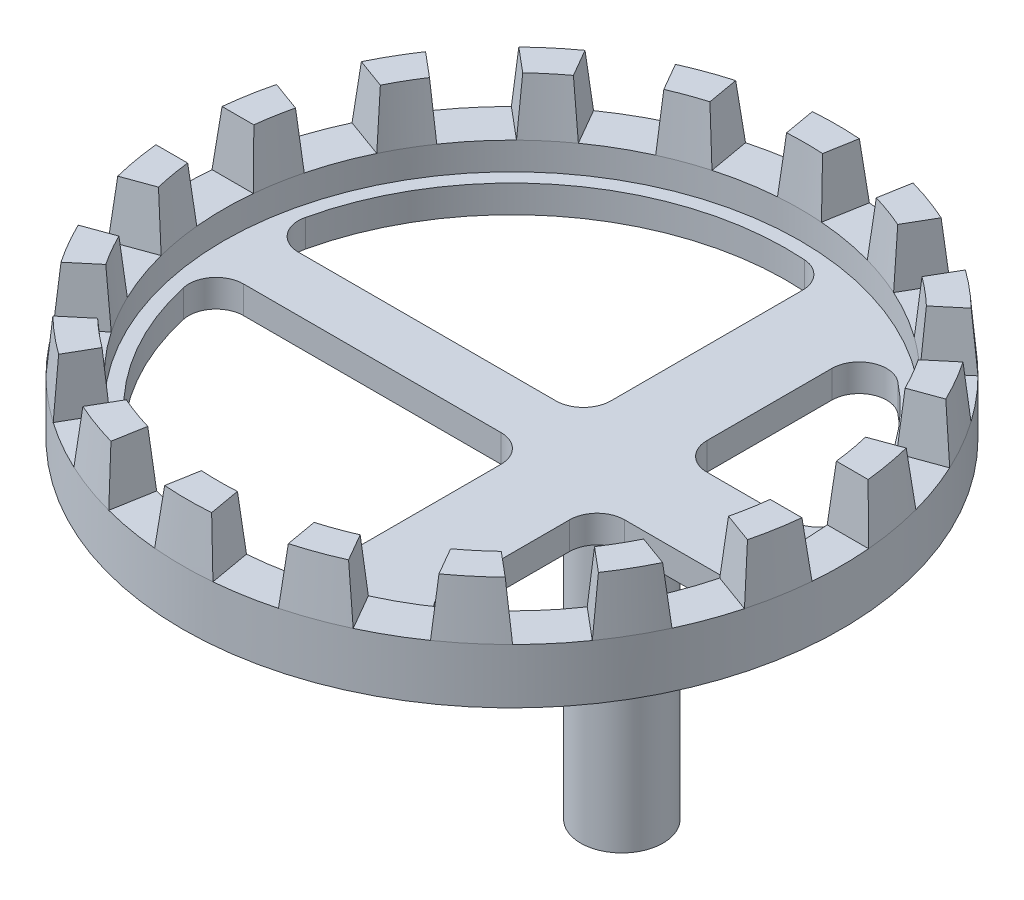
SolidWorks part; units mm, degrees
ref_plane "Front Plane" through (0, 0, 0) normal (0, 0, 1) x (1, 0, 0)
ref_plane "Top Plane" through (0, 0, 0) normal (0, 1, 0) x (1, 0, 0)
ref_plane "Right Plane" through (0, 0, 0) normal (1, 0, 0) x (0, 0, -1)
sketch "Sketch1" plane through (0, 0, 0) normal (0, 1, 0) x (1, 0, 0)
  circle A0 centre (0, 0) radius 7.5
  circle A1 centre (-20, 0) radius 60
  point P5 (0, 0)
  dimension "D1" = 20
  dimension "D2" = 15
  dimension "D3" = 120
extrude "Boss-Extrude1" add sketch "Sketch1" along normal blind 5 contours A1 A0 | A0 region at (0, 0, 0) region at (-20.3175, 0, 0)
extrude "Boss-Extrude2" add sketch "Sketch1<3>" against normal blind 50 contours A0 region at (0, 0, 0)
sketch "Sketch1<3>" plane through (0, 0, 0) normal (0, 1, 0) x (1, 0, 0) same geometry as "Sketch1"
sketch "Sketch2" plane through (0, 5, 0) normal (0, 1, 0) x (1, 0, 0)
  line L0 (-70, 0) -> (-20, 0) construction
  line L1 (-20, 0) -> (30, 0) construction
  line L2 (3, 35.2278) -> (3, 12.5)
  line L3 (-12, 44.8999) -> (-12, 10)
  line L4 (-17, 5) -> (-63.8748, 5)
  line L5 (-17, -5) -> (-63.8748, -5)
  line L6 (8, 7.5) -> (23.229, 7.5)
  line L7 (8, -7.5) -> (29.4343, -7.5)
  line L8 (3, -12.5) -> (3, -35.2278)
  line L9 (-12, -10) -> (-12, -44.8999)
  arc A0 (-68.7498, -11.1111) -> (-16.6667, -49.8888) centre (-20, 0) ccw
  arc A1 (-16.6667, 49.8888) -> (-68.7498, 11.1111) centre (-20, 0) ccw
  arc A2 (28.0323, 13.8889) -> (11.1111, 39.142) centre (-20, 0) ccw
  arc A3 (11.1111, -39.142) -> (29.4343, -7.5) centre (-20, 0) ccw
  arc A4 (-63.8748, 5) -> (-68.7498, 11.1111) centre (-63.8748, 10) cw
  arc A5 (23.229, 7.5) -> (28.0323, 13.8889) centre (23.229, 12.5) ccw
  arc A6 (3, 35.2278) -> (11.1111, 39.142) centre (8, 35.2278) cw
  arc A7 (-63.8748, -5) -> (-68.7498, -11.1111) centre (-63.8748, -10) ccw
  arc A8 (-12, -44.8999) -> (-16.6667, -49.8888) centre (-17, -44.8999) cw
  arc A9 (3, -35.2278) -> (11.1111, -39.142) centre (8, -35.2278) ccw
  arc A10 (8, -7.5) -> (3, -12.5) centre (8, -12.5) ccw
  arc A11 (8, 7.5) -> (3, 12.5) centre (8, 12.5) cw
  arc A12 (-17, -5) -> (-12, -10) centre (-17, -10) cw
  arc A13 (-17, 5) -> (-12, 10) centre (-17, 10) ccw
  arc A14 (-12, 44.8999) -> (-16.6667, 49.8888) centre (-17, 44.8999) ccw
  point P19 (-69.7494, 5)
  point P22 (29.4343, 7.5)
  point P27 (-69.7494, -5)
  point P32 (3, -44.3959)
  point P35 (3, -7.5)
  point P38 (3, 7.5)
  point P41 (-12, -5)
  point P44 (-12, 5)
  point P47 (-12, 49.3559)
  dimension "D1" = 100
  dimension "D6" = 5
  dimension "D2" = 12
  dimension "D3" = 15
  dimension "D4" = 10
  dimension "D5" = 15
extrude "Cut-Extrude1" cut sketch "Sketch2" against normal up to surface (5 mm away) up to face at (0, 0, 7.5)
sketch "Sketch3" plane through (0, 5, 0) normal (0, 1, 0) x (1, 0, 0)
  circle A0 centre (-20, 0) radius 52.5
  circle A1 centre (-20, 0) radius 60 construction
  circle A2 centre (-20, 0) radius 60
  circle M24 centre (-20, 0) radius 60
  dimension "D1" = 105
extrude "Boss-Extrude3" add sketch "Sketch3" along normal blind 5 contours A0 M24 region at (-78.3029, 5, 0)
sketch "Sketch4" plane through (0, 10, 0) normal (0, 1, 0) x (1, 0, 0)
  line L0 (-20, 60) -> (-20, 0) construction
  line L1 (-25.3079, 59.7648) -> (-24, 52.3474)
  line L2 (-14.6921, 59.7648) -> (-16, 52.3474)
  circle A0 centre (-20, 0) radius 60 construction
  circle A1 centre (-20, 0) radius 52.5 construction
  arc A2 (-16, 52.3474) -> (-24, 52.3474) centre (-20, 0) ccw
  arc A3 (-14.6921, 59.7648) -> (-25.3079, 59.7648) centre (-20, 0) ccw
  dimension "D1" = 10
  dimension "D2" = 4
extrude "Boss-Extrude4" add sketch "Sketch4" along normal blind 10 draft 5
pattern_circular "CirPattern1" count 18 over 360 about axis through (-20, 5, 0) along (0, -1, 0) of "Boss-Extrude4" reverse direction yes
